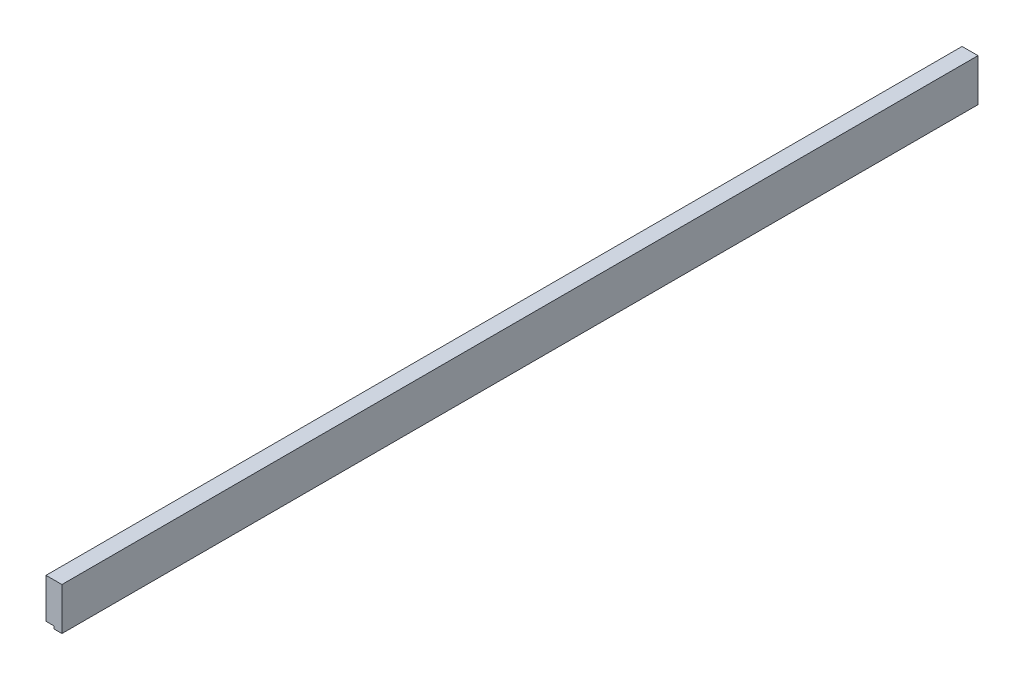
SolidWorks part; units mm, degrees
ref_plane "Front Plane" through (0, 0, 0) normal (0, 0, 1) x (1, 0, 0)
ref_plane "Top Plane" through (0, 0, 0) normal (0, 1, 0) x (1, 0, 0)
ref_plane "Right Plane" through (0, 0, 0) normal (1, 0, 0) x (0, 0, -1)
sketch "Sketch1" plane through (0, 0, 0) normal (1, 0, 0) x (0, 0, -1)
  line L1 (1095.375, 50.8) -> (-1095.375, 50.8)
  line L2 (1095.375, 50.8) -> (1095.375, -50.8)
  line L3 (1095.375, -50.8) -> (-1095.375, -50.8)
  line L4 (-1095.375, 50.8) -> (-1095.375, -50.8)
  line L5 (1095.375, 50.8) -> (-1095.375, -50.8) construction
  line L6 (1095.375, -50.8) -> (-1095.375, 50.8) construction
  point P0 (0, 0)
  dimension "D1" = 101.6
  dimension "D2" = 2190.75
extrude "Boss-Extrude1" add sketch "Sketch1" along normal blind 38.1
sketch "Sketch3" plane through (0, 0, 0) normal (-1, 0, 0) x (0, 0, 1)
  line L0 (1095.375, -50.8) -> (-1095.375, -50.8) construction
  line L1 (-695.325, -50.8) -> (-609.6, -50.8)
  line L2 (-695.325, -50.8) -> (-695.325, -25.4)
  line L3 (-695.325, -25.4) -> (-609.6, -25.4)
  line L4 (-609.6, -50.8) -> (-609.6, -25.4)
  line L5 (1095.375, 50.8) -> (1095.375, -50.8) construction
  line L6 (-585.7875, -50.8) -> (471.4875, -50.8)
  line L7 (-585.7875, -50.8) -> (-585.7875, -12.7)
  line L8 (-585.7875, -12.7) -> (471.4875, -12.7)
  line L9 (471.4875, -50.8) -> (471.4875, -12.7)
  line L10 (495.3, -50.8) -> (581.025, -50.8)
  line L11 (495.3, -50.8) -> (495.3, -25.4)
  line L12 (495.3, -25.4) -> (581.025, -25.4)
  line L13 (581.025, -50.8) -> (581.025, -25.4)
  line L14 (663.575, -50.8) -> (1095.375, -50.8)
  line L15 (663.575, -50.8) -> (663.575, -44.45)
  line L16 (663.575, -44.45) -> (1095.375, -44.45)
  line L17 (1095.375, -50.8) -> (1095.375, -44.45)
  line L18 (-1095.375, -50.8) -> (-1095.375, 50.8) construction
  line M14 (1095.375, -50.8) -> (1095.375, 50.8)
  line M17 (-1095.375, -50.8) -> (1095.375, -50.8)
  dimension "D1" = 38.1
  dimension "D2" = 23.8125
  dimension "D3" = 1057.275
  dimension "D4" = 6.35
  dimension "D5" = 431.8
  dimension "D6" = 85.725
  dimension "D7" = 85.725
  dimension "D8" = 25.4
  dimension "D9" = 400.05
  dimension "D10" = 23.8125
extrude "Cut-Extrude1" cut sketch "Sketch3" against normal blind 19.05 contours L9 L8 L7 M17 | L16 L15 M17 M14 region at (0, -47.625, 879.475) region at (0, -31.75, -57.15)
extrude "Cut-Extrude2" cut sketch "Sketch3<3>" against normal blind 9.525 contours L13 L12 L11 M17 | L4 L3 L2 M17 region at (0, -38.1, -652.4625) region at (0, -38.1, 538.1625)
sketch "Sketch3<3>" plane through (0, 0, 0) normal (-1, 0, 0) x (0, 0, 1) same geometry as "Sketch3"
